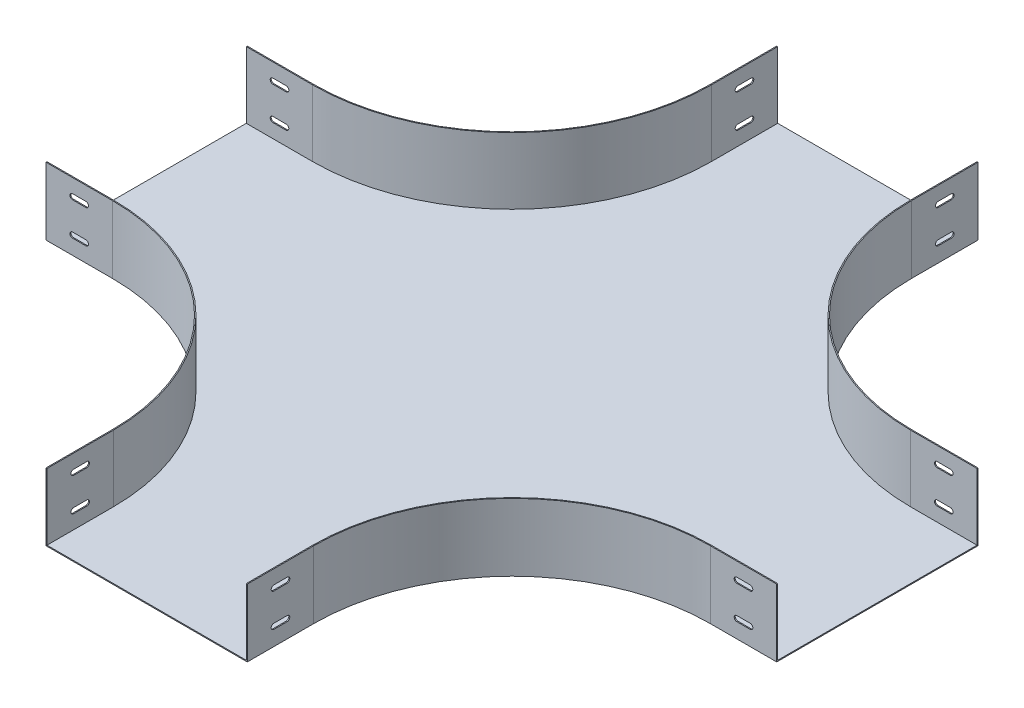
SolidWorks part; units mm, degrees
ref_plane "Front Plane" through (0, 0, 0) normal (0, 0, 1) x (1, 0, 0)
ref_plane "Top Plane" through (0, 0, 0) normal (0, 1, 0) x (1, 0, 0)
ref_plane "Right Plane" through (0, 0, 0) normal (1, 0, 0) x (0, 0, -1)
sketch "Sketch1" plane through (0, 0, 0) normal (0, 1, 0) x (1, 0, 0)
  line L0 (-150, 550) -> (150, 550)
  line L1 (-150, -550) -> (150, -550)
  line L2 (550, 150) -> (550, -150)
  line L3 (-550, 150) -> (-550, -150)
  line L4 (150, -550) -> (150, -450)
  line L5 (550, -150) -> (450, -150)
  line L6 (150, 550) -> (150, 450)
  line L7 (-150, 550) -> (-150, 450)
  line L8 (-550, 150) -> (-450, 150)
  line L9 (-550, -150) -> (-450, -150)
  line L10 (-150, -550) -> (-150, -450)
  line L11 (550, 150) -> (450, 150)
  line L12 (0, 550) -> (0, -550) construction
  line L13 (-550, 0) -> (550, 0) construction
  arc A0 (-450, -150) -> (-150, -450) centre (-450, -450) cw
  arc A1 (-450, 150) -> (-150, 450) centre (-450, 450) ccw
  arc A2 (150, 450) -> (450, 150) centre (450, 450) ccw
  arc A3 (150, -450) -> (450, -150) centre (450, -450) cw
  dimension "Radius" = 300
  dimension "Width" = 300
  dimension "Length" = 1100
extrude "Boss-Extrude1" add sketch "Sketch1" against normal blind 1.5
sketch "Sketch2" plane through (0, 0, 0) normal (0, 1, 0) x (1, 0, 0)
  line L0 (150, -550) -> (150, -450) construction
  line L1 (450, -150) -> (550, -150) construction
  line L2 (150, -550) -> (150, -450)
  line L3 (450, -150) -> (550, -150)
  line L4 (550, 150) -> (450, 150) construction
  line L5 (150, 450) -> (150, 550) construction
  line L6 (-150, 550) -> (-150, 450) construction
  line L7 (-450, 150) -> (-550, 150) construction
  line L8 (-550, -150) -> (-450, -150) construction
  line L9 (-150, -450) -> (-150, -550) construction
  line L10 (550, 150) -> (450, 150)
  line L11 (150, 450) -> (150, 550)
  line L12 (-150, 550) -> (-150, 450)
  line L13 (-450, 150) -> (-550, 150)
  line L14 (-550, -150) -> (-450, -150)
  line L15 (-150, -450) -> (-150, -550)
  arc A0 (450, -150) -> (150, -450) centre (450, -450) ccw construction
  arc A1 (450, -150) -> (150, -450) centre (450, -450) ccw
  arc A2 (150, 450) -> (450, 150) centre (450, 450) ccw construction
  arc A3 (-450, 150) -> (-150, 450) centre (-450, 450) ccw construction
  arc A4 (-150, -450) -> (-450, -150) centre (-450, -450) ccw construction
  arc A5 (150, 450) -> (450, 150) centre (450, 450) ccw
  arc A6 (-450, 150) -> (-150, 450) centre (-450, 450) ccw
  arc A7 (-150, -450) -> (-450, -150) centre (-450, -450) ccw
extrude "Extrude-Thin1" add sketch "Sketch2" along normal blind 100 and the other way up to surface (1.5 mm away) thin other way up to face at (0, -1.5, 0) thin type one direction wall 1.5
sketch "Sketch3" plane through (0, 0, 0) normal (0, 0, 1) x (1, 0, 0)
  line L0 (490, 75) -> (510, 75) construction
  line L1 (490, 79) -> (510, 79)
  line L2 (490, 71) -> (510, 71)
  line L3 (490, 25) -> (510, 25) construction
  line L4 (490, 29) -> (510, 29)
  line L5 (490, 21) -> (510, 21)
  line L6 (450, 50) -> (550, 50) construction
  line L7 (550, -1.5) -> (550, 100) construction
  line L8 (-510, 75) -> (-490, 75) construction
  line L9 (500, 0) -> (500, 50) construction
  line L10 (-510, 79) -> (-490, 79)
  line L11 (500, 50) -> (500, 100) construction
  line L12 (-510, 71) -> (-490, 71)
  line L13 (-510, 25) -> (-490, 25) construction
  line L14 (-510, 29) -> (-490, 29)
  line L15 (-510, 21) -> (-490, 21)
  line L16 (-550, 50) -> (-450, 50) construction
  line L17 (-500, 0) -> (-500, 50) construction
  line L18 (-500, 50) -> (-500, 100) construction
  line L19 (-550, 100) -> (-550, -1.5) construction
  arc A0 (490, 79) -> (490, 71) centre (490, 75) ccw
  arc A1 (510, 71) -> (510, 79) centre (510, 75) ccw
  arc A2 (490, 29) -> (490, 21) centre (490, 25) ccw
  arc A3 (510, 21) -> (510, 29) centre (510, 25) ccw
  arc A4 (-510, 79) -> (-510, 71) centre (-510, 75) ccw
  arc A5 (-490, 71) -> (-490, 79) centre (-490, 75) ccw
  arc A6 (-510, 29) -> (-510, 21) centre (-510, 25) ccw
  arc A7 (-490, 21) -> (-490, 29) centre (-490, 25) ccw
  point P2 (500, 75)
  point P8 (500, 25)
  point P22 (-500, 75)
  point P30 (-500, 25)
  dimension "D1" = 4
  dimension "D2" = 20
  dimension "D3" = 50
  dimension "D4" = 100
  dimension "D5" = 50
extrude "Cut-Extrude1" cut sketch "Sketch3" against normal through all and the other way through all
sketch "Sketch4" plane through (0, 0, 0) normal (1, 0, 0) x (0, 0, -1)
  line L0 (-550, 50) -> (-450, 50) construction
  line L1 (-550, -1.5) -> (-550, 100) construction
  line L2 (450, 50) -> (550, 50) construction
  line L3 (-500, 100) -> (-500, 50) construction
  line L4 (500, 100) -> (500, 50) construction
  line L5 (-500, 50) -> (-500, 0) construction
  line L6 (500, 50) -> (500, 0) construction
  line L7 (-510, 75) -> (-490, 75) construction
  line L8 (-510, 79) -> (-490, 79)
  line L9 (-510, 71) -> (-490, 71)
  line L10 (-510, 25) -> (-490, 25) construction
  line L11 (-510, 29) -> (-490, 29)
  line L12 (-510, 21) -> (-490, 21)
  line L13 (490, 75) -> (510, 75) construction
  line L14 (490, 79) -> (510, 79)
  line L15 (490, 71) -> (510, 71)
  line L16 (490, 25) -> (510, 25) construction
  line L17 (490, 29) -> (510, 29)
  line L18 (490, 21) -> (510, 21)
  line L19 (550, 100) -> (550, -1.5) construction
  arc A0 (-510, 79) -> (-510, 71) centre (-510, 75) ccw
  arc A1 (-490, 71) -> (-490, 79) centre (-490, 75) ccw
  arc A2 (-510, 29) -> (-510, 21) centre (-510, 25) ccw
  arc A3 (-490, 21) -> (-490, 29) centre (-490, 25) ccw
  arc A4 (490, 79) -> (490, 71) centre (490, 75) ccw
  arc A5 (510, 71) -> (510, 79) centre (510, 75) ccw
  arc A6 (490, 29) -> (490, 21) centre (490, 25) ccw
  arc A7 (510, 21) -> (510, 29) centre (510, 25) ccw
  point P15 (-500, 75)
  point P21 (-500, 25)
  point P29 (500, 75)
  point P35 (500, 25)
  dimension "D1" = 4
  dimension "D2" = 20
  dimension "D5" = 50
  dimension "D3" = 100
  dimension "D4" = 50
extrude "Cut-Extrude2" cut sketch "Sketch4" against normal through all and the other way through all
sketch "Sketch5" plane through (0, 0, 0) normal (0, 1, 0) x (1, 0, 0)
  line L0 (-150, -550) -> (150, -550) construction
  line L1 (550, -150) -> (550, 150) construction
  line L2 (150, 550) -> (-150, 550) construction
  line L3 (-550, 150) -> (-550, -150) construction
  point P0 (0, -550)
  point P1 (550, 0)
  point P4 (0, 550)
  point P7 (-550, 0)
  point P10 (0, 0)
other "CPoint1" parameters "Diameter"=10, "StubLength"=300
ref_axis "Axis1" through (560, 0, 0) along (-1, 0, 0)
other "CPoint2" parameters "Diameter"=10, "StubLength"=300
ref_axis "Axis2" through (-560, 0, 0) along (1, 0, 0)
other "CPoint3" parameters "Diameter"=10, "StubLength"=300
ref_axis "Axis3" through (0, 0, 560) along (0, 0, -1)
other "CPoint4" parameters "Diameter"=10, "StubLength"=300
ref_axis "Axis4" through (0, 0, -560) along (0, 0, 1)
other "RPoint1"
equation "\"D5@Extrude-Thin1\"=\"Thickness@Boss-Extrude1\""
equation "\"D3@Sketch3\"=\"Height@Extrude-Thin1\"/2"
equation "\"D5@Sketch3\"=\"Height@Extrude-Thin1\"/2"
equation "\"D4@Sketch4\"=\"Height@Extrude-Thin1\"/2"
equation "\"D5@Sketch4\"=\"Height@Extrude-Thin1\"/2"
